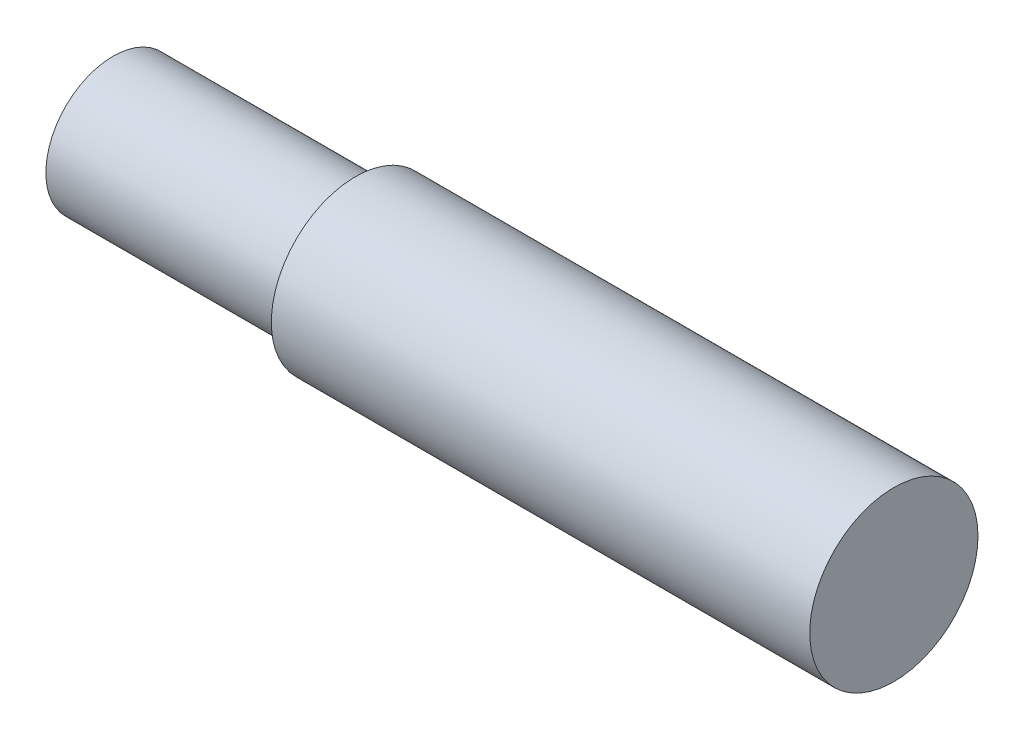
SolidWorks part; units mm, degrees
ref_plane "Front Plane" through (0, 0, 0) normal (0, 0, 1) x (1, 0, 0)
ref_plane "Top Plane" through (0, 0, 0) normal (0, 1, 0) x (1, 0, 0)
ref_plane "Right Plane" through (0, 0, 0) normal (1, 0, 0) x (0, 0, -1)
sketch "Sketch2" plane through (0, 0, 0) normal (1, 0, 0) x (0, 0, -1)
  circle A0 centre (0, 0) radius 3.9688
  dimension "D1" = 7.9375
extrude "Boss-Extrude1" add sketch "Sketch2" along normal blind 25.4
sketch "Sketch3" plane through (0, 0, 0) normal (1, 0, 0) x (0, 0, -1)
  circle A0 centre (0, 0) radius 3.175
  dimension "D1" = 6.35
extrude "Boss-Extrude2" add sketch "Sketch3" against normal blind 11.43
